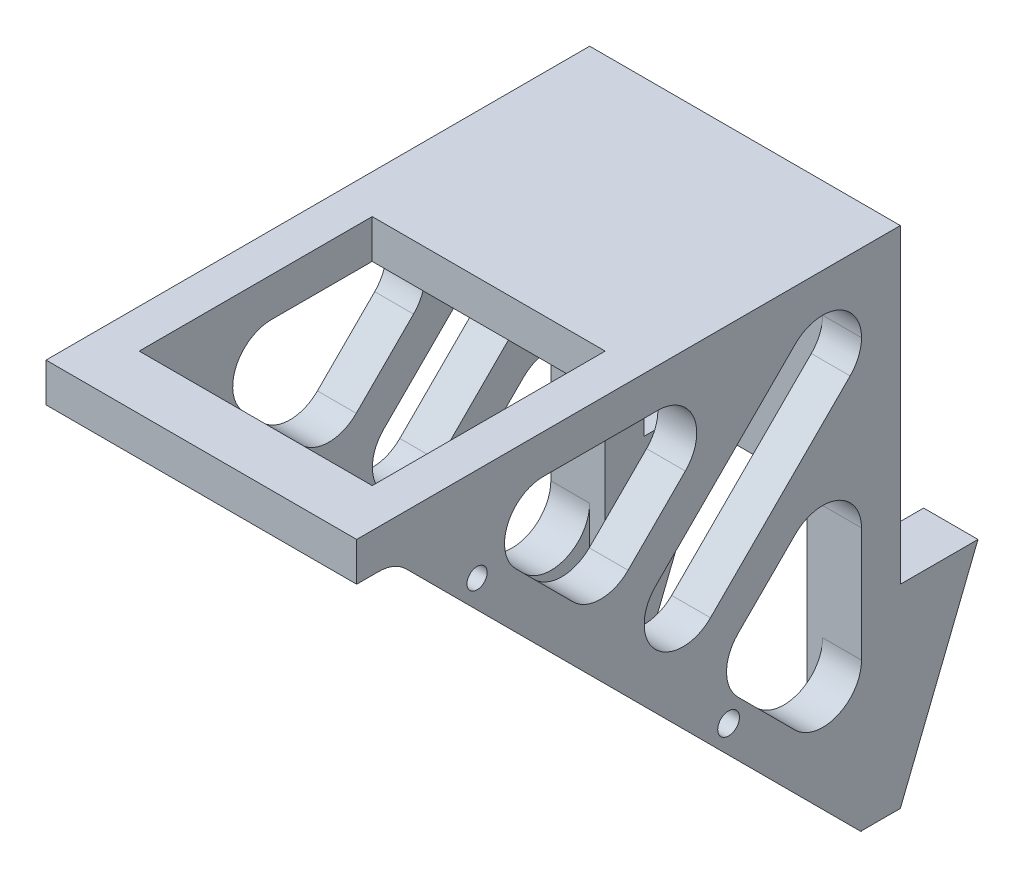
SolidWorks part; units mm, degrees
ref_plane "Front" through (0, 0, 0) normal (0, 0, 1) x (1, 0, 0)
ref_plane "Top" through (0, 0, 0) normal (0, 1, 0) x (1, 0, 0)
ref_plane "Right" through (0, 0, 0) normal (1, 0, 0) x (0, 0, -1)
sketch "Esquisse1" plane through (0, 0, 0) normal (0, 0, 1) x (1, 0, 0)
  line L1 (-25.4, 41.275) -> (25.4, 41.275)
  line L2 (-25.4, 41.275) -> (-25.4, -41.275)
  line L3 (-25.4, -41.275) -> (25.4, -41.275)
  line L4 (25.4, 41.275) -> (25.4, -41.275)
  line L5 (-25.4, 41.275) -> (25.4, -41.275) construction
  line L6 (-25.4, -41.275) -> (25.4, 41.275) construction
  point P1 (0, 0)
  dimension "D1" = 50.8
  dimension "D2" = 82.55
extrude "Boss.-Extru.1" add sketch "Esquisse1" along normal blind 6.35
sketch "Esquisse2" plane through (0, 41.275, 0) normal (0, 1, 0) x (1, 0, 0)
  line L0 (25.4, -6.35) -> (25.4, 0) construction
  line L1 (-25.4, -6.35) -> (25.4, -6.35)
  line L2 (-25.4, -6.35) -> (-25.4, -88.9)
  line L3 (-25.4, -88.9) -> (25.4, -88.9)
  line L4 (25.4, -6.35) -> (25.4, -88.9)
  dimension "D1" = 82.55
extrude "Boss.-Extru.2" add sketch "Esquisse2" against normal blind 6.35
sketch "Esquisse4" plane through (-25.4, 0, 0) normal (-1, 0, 0) x (0, 0, 1)
  line L0 (6.35, -36.917) -> (78.192, 34.925) construction
  line L3 (6.35, 34.925) -> (6.35, -41.275) construction
  line L4 (6.35, 34.925) -> (88.9, 34.925) construction
  line L5 (6.35, -32.4269) -> (31.0457, -7.7312)
  line L6 (6.35, -41.4072) -> (82.6822, 34.925)
  line L13 (35.5358, -3.2411) -> (6.35, 25.9447)
  line L14 (6.35, 25.9447) -> (6.35, 16.9645)
  line L15 (6.35, 16.9645) -> (31.0457, -7.7312)
  line L16 (44.5161, 5.7392) -> (15.3303, 34.925)
  line L17 (15.3303, 34.925) -> (24.3105, 34.925)
  line L18 (24.3105, 34.925) -> (49.0062, 10.2293)
  line L19 (6.35, 34.925) -> (40.026, 1.249) construction
  line L20 (6.35, -41.4072) -> (6.35, -32.4269)
  line L21 (82.6822, 34.925) -> (73.7019, 34.925)
  line L22 (49.0062, 10.2293) -> (73.7019, 34.925)
  line L23 (35.5358, -3.2411) -> (44.5161, 5.7392)
  circle A0 centre (28.0822, -15.1848) radius 1.778
  circle A1 centre (69.2118, 25.9447) radius 1.651
  dimension "D1" = 3.302
  dimension "D2" = 3.556
  dimension "D3" = 58.166
  dimension "D4" = 107.95
  dimension "D5" = 45
  dimension "D6" = 12.7
  dimension "D7" = 3.175
  dimension "D8" = 6.35
  dimension "D10" = 6.35
  dimension "D11" = 6.35
  dimension "D12" = 6.35
  dimension "D13" = 6.35
extrude "Boss.-Extru.3" add sketch "Esquisse4" against normal blind 6.35
mirror "Symétrie1" about plane through (0, 0, 0) normal (1, 0, 0) of "Boss.-Extru.3"
sketch "Esquisse5" plane through (0, 41.275, 0) normal (0, 1, 0) x (1, 0, 0)
  line L0 (25.4, -88.9) -> (25.4, 0) construction
  line L1 (19.05, -80.01) -> (-19.05, -80.01)
  line L2 (19.05, -80.01) -> (19.05, -41.91)
  line L3 (19.05, -41.91) -> (-19.05, -41.91)
  line L4 (-19.05, -80.01) -> (-19.05, -41.91)
  line L5 (-25.4, -88.9) -> (-25.4, 0) construction
  line L6 (-25.4, -88.9) -> (25.4, -88.9) construction
  dimension "D1" = 6.35
  dimension "D2" = 6.35
  dimension "D3" = 8.89
  dimension "D4" = 38.1
extrude "Enlèv. mat.-Extru.1" cut sketch "Esquisse5" against normal blind 6.35
sketch "Esquisse7" plane through (0, 0, 0) normal (0, 0, -1) x (-1, 0, 0)
  line L0 (25.4, -41.275) -> (-25.4, -41.275) construction
  line L1 (-16.51, 3.175) -> (16.51, 3.175)
  line L2 (-16.51, 3.175) -> (-16.51, -41.275)
  line L3 (-16.51, -41.275) -> (16.51, -41.275)
  line L4 (16.51, 3.175) -> (16.51, -41.275)
  line L5 (25.4, 41.275) -> (25.4, -41.275) construction
  line L6 (-25.4, -41.275) -> (-25.4, 41.275) construction
  dimension "D1" = 8.89
  dimension "D2" = 8.89
  dimension "D3" = 44.45
extrude "Enlèv. mat.-Extru.2" cut sketch "Esquisse7" against normal blind 6.35
sketch "Esquisse8" plane through (25.4, 0, 0) normal (1, 0, 0) x (0, 0, -1)
  line L0 (0, -41.275) -> (12.7, -9.525)
  line L1 (12.7, -9.525) -> (0, -9.525)
  line L2 (0, -9.525) -> (0, -41.275)
extrude "Boss.-Extru.4" add sketch "Esquisse8" against normal blind 8.89
mirror "Symétrie2" about plane through (0, 0, 0) normal (1, 0, 0) of "Boss.-Extru.4"
fillet "Congé1" radius 6.35 23 edges at (22.225, -32.4269, 6.35) (22.225, -7.7312, 31.0457) (22.225, 16.9645, 6.35) (22.225, -3.2411, 35.5358) (22.225, 5.7392, 44.5161) (22.225, 10.2293, 49.0062) (22.225, 34.925, 73.7019) (22.225, 34.925, 15.3303) (22.225, 25.9447, 6.35) (22.225, 34.925, 24.3105) (-22.225, 16.9645, 6.35) (-22.225, -32.4269, 6.35) (-22.225, -7.7312, 31.0457) (-22.225, 5.7392, 44.5161) (-22.225, -3.2411, 35.5358) (-22.225, 10.2293, 49.0062) (-22.225, 34.925, 73.7019) (-22.225, 25.9447, 6.35) (-22.225, 34.925, 15.3303) (-22.225, 34.925, 24.3105) (0, 34.925, 6.35) (22.225, 34.925, 82.6822) (-22.225, 34.925, 82.6822)
